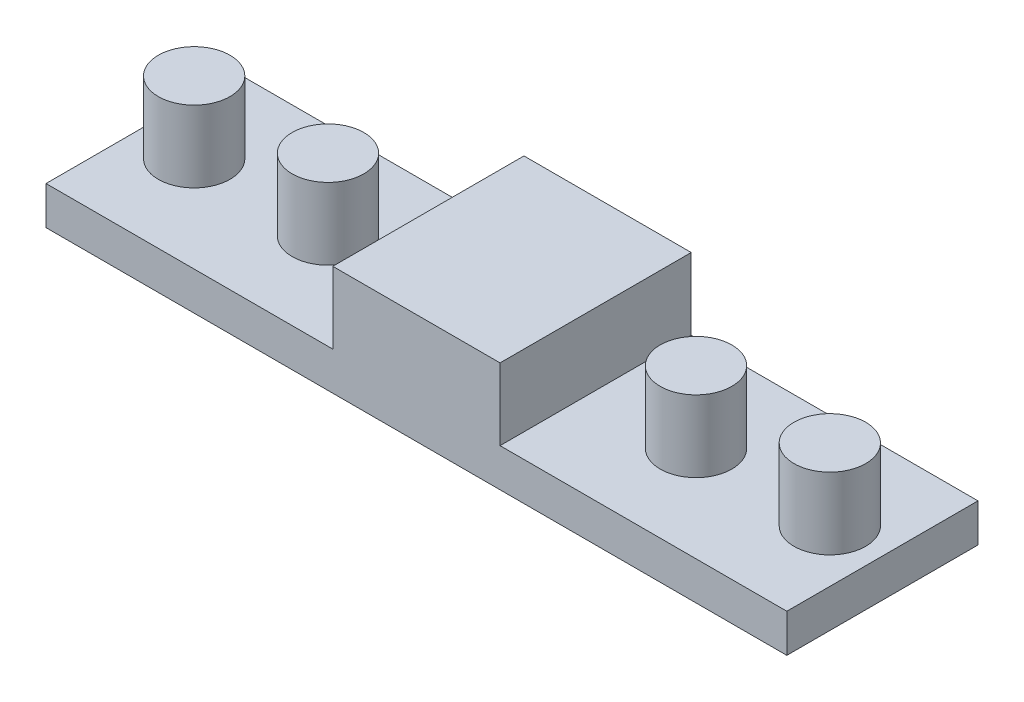
SolidWorks part; units mm, degrees
ref_plane "Спереди" through (0, 0, 0) normal (0, 0, 1) x (1, 0, 0)
ref_plane "Сверху" through (0, 0, 0) normal (0, 1, 0) x (1, 0, 0)
ref_plane "Справа" through (0, 0, 0) normal (1, 0, 0) x (0, 0, -1)
sketch "Эскиз1" plane through (0, 0, 0) normal (0, 1, 0) x (1, 0, 0)
  line L1 (-7.75, -2) -> (7.75, -2)
  line L2 (-7.75, -2) -> (-7.75, 2)
  line L3 (-7.75, 2) -> (7.75, 2)
  line L4 (7.75, -2) -> (7.75, 2)
  line L5 (-7.75, -2) -> (7.75, 2) construction
  line L6 (-7.75, 2) -> (7.75, -2) construction
  line L7 (-1.75, -2) -> (1.75, -2)
  line L8 (-1.75, -2) -> (-1.75, 2)
  line L9 (-1.75, 2) -> (1.75, 2)
  line L10 (1.75, -2) -> (1.75, 2)
  line L11 (-1.75, -2) -> (1.75, 2) construction
  line L12 (-1.75, 2) -> (1.75, -2) construction
  point P0 (0, 0)
  point P6 (0, 0)
  dimension "D1" = 4
  dimension "D2" = 15.5
  dimension "D3" = 3.5
extrude "Бобышка-Вытянуть1" add sketch "Эскиз1" along normal blind 0.8 contours L1 L10 L3 L8 | L1 L8 L3 L2 | L10 L1 L4 L3 region at (-4.75, 0, 0) region at (0, 0, 0) region at (4.75, 0, 0)
extrude "Бобышка-Вытянуть2" add sketch "Эскиз1<3>" along normal blind 1.5 from surface contours L1 L10 L3 L8 region at (0, 0, 0) starting at face at (0, 0.8, 0)
sketch "Эскиз1<3>" plane through (0, 0, 0) normal (0, 1, 0) x (1, 0, 0) same geometry as "Эскиз1"
sketch "Эскиз2" plane through (0, 0.8, 0) normal (0, 1, 0) x (1, 0, 0)
  line L1 (0, 7.0186) -> (0, -4.9291) construction
  line L2 (-7.75, -2) -> (-7.75, 2) construction
  circle A0 centre (-3.85, 0) radius 0.75
  circle A1 centre (-6.65, 0) radius 0.75
  circle A2 centre (6.65, 0) radius 0.75
  circle A3 centre (3.85, 0) radius 0.75
  point P4 (-7.75, 0)
  dimension "D3" = 2.8
  dimension "D4" = 1.5
  dimension "D1" = 1.1
  dimension "D2" = 2
extrude "Бобышка-Вытянуть3" add sketch "Эскиз2" along normal blind 1.5
